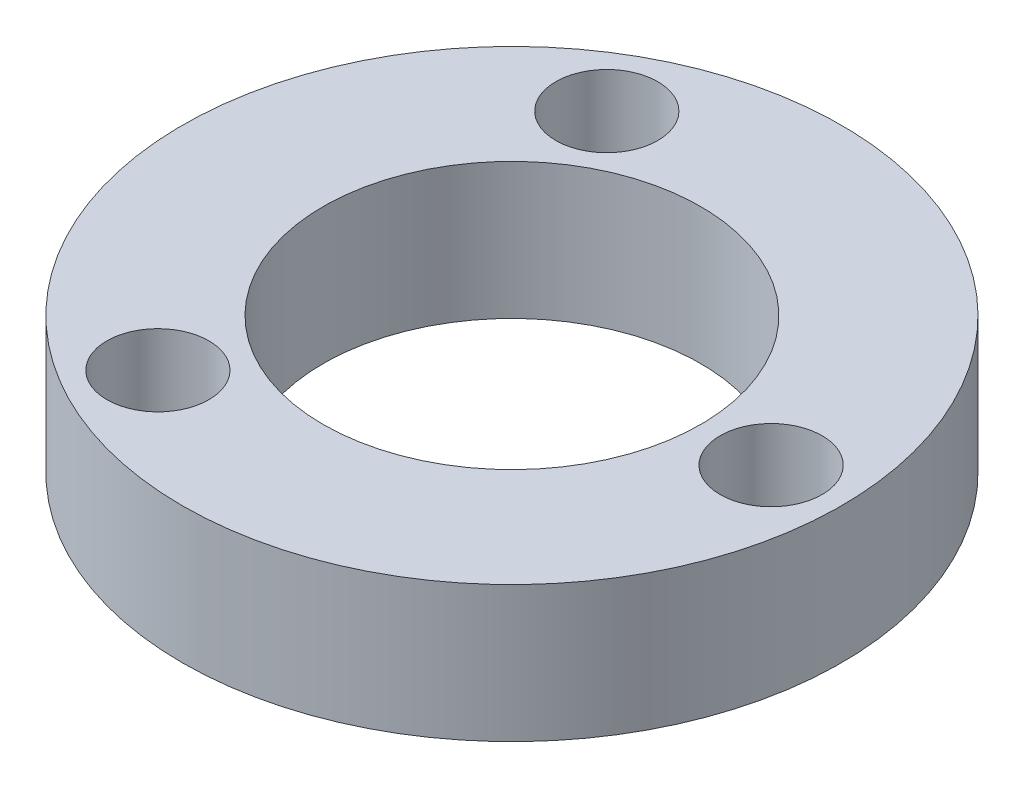
SolidWorks part; units mm, degrees
material "ABS"
ref_plane "Front Plane" through (0, 0, 0) normal (0, 0, 1) x (1, 0, 0)
ref_plane "Top Plane" through (0, 0, 0) normal (0, 1, 0) x (1, 0, 0)
ref_plane "Right Plane" through (0, 0, 0) normal (1, 0, 0) x (0, 0, -1)
sketch "Sketch1" plane through (0, 0, 0) normal (0, 1, 0) x (1, 0, 0)
  circle A2 centre (-9.5263, -16.4999) radius 3.175 construction
  circle A3 centre (-9.5262, 16.4999) radius 3.175 construction
  circle A4 centre (19.0525, 0) radius 3.175 construction
  circle A5 centre (-9.5262, 16.4999) radius 3.175
  circle A6 centre (19.0525, 0) radius 3.175
  circle A7 centre (-9.5263, -16.4999) radius 3.175
  circle A15 centre (0, 0) radius 13.8775
  circle A16 centre (0, 0) radius 24.2275
  point P1 (30.1365, 0)
  point P12 (-9.5263, -16.4999)
  point P14 (19.0525, 0)
  point P16 (-9.5262, 16.4999)
  point P20 (-4.9245, 20.2425)
  point P29 (-4.9245, -20.2425)
  dimension "D3" = 6.35
  dimension "D2" = 19.0525
extrude "Boss-Extrude1" add sketch "Sketch1" along normal blind 10 contours A7 | A5 | A6 | A5 A6 A7 region at (-9.5262, 0, -16.4999) region at (19.0525, 0, 0) region at (-9.5262, 0, 16.4999) region at (-23.5422, 0, 0)
sketch "Sketch3" plane through (0, 10, 0) normal (0, 1, 0) x (1, 0, 0)
  circle A1 centre (19.0525, 0) radius 3.75
  dimension "D1" = 7.5
extrude "Cut-Extrude1" cut sketch "Sketch3" against normal blind 7.5
sketch "Sketch5" plane through (0, 0, 0) normal (0, 0, 1) x (1, 0, 0)
  line L0 (0, 0) -> (0, 1.348) construction
pattern_circular "CirPattern1" count 3 every 120 about axis through (0, 0, 0) along (0, 1, 0) of "Cut-Extrude1"
